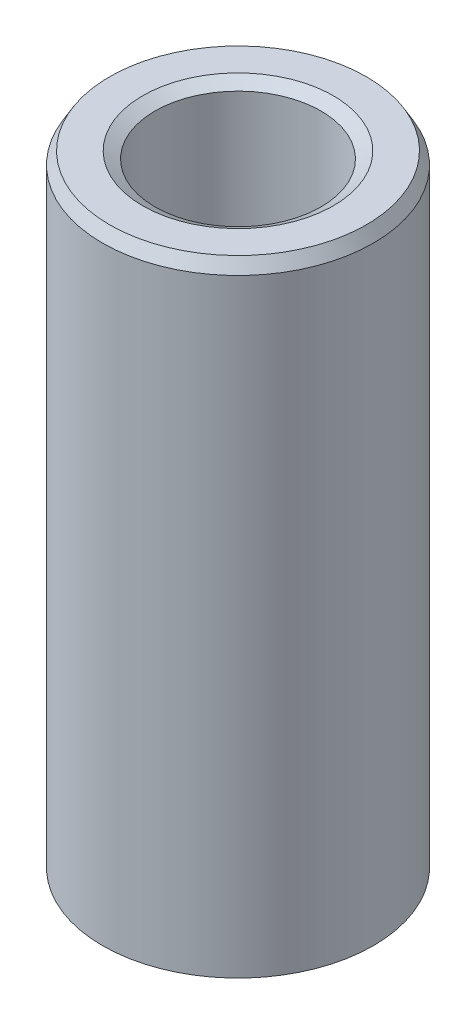
SolidWorks part; units mm, degrees
ref_plane "Front Plane" through (0, 0, 0) normal (0, 0, 1) x (1, 0, 0)
ref_plane "Top Plane" through (0, 0, 0) normal (0, 1, 0) x (1, 0, 0)
ref_plane "Right Plane" through (0, 0, 0) normal (1, 0, 0) x (0, 0, -1)
sketch "Sketch1" plane through (0, 0, 0) normal (0, 1, 0) x (1, 0, 0)
  circle A0 centre (0, 0) radius 42.5
  dimension "SLEEVE_OD" = 85
extrude "Boss-Extrude1" add sketch "Sketch1" along normal blind 197.0313
sketch "Sketch2" plane through (0, 0, 0) normal (0, 1, 0) x (1, 0, 0)
  circle A0 centre (0, 0) radius 26.072
  dimension "BORE_D" = 52.144
extrude "Cut-Extrude1" cut sketch "Sketch2" along normal through all
chamfer "Chamfer1" distance 3.8548 angle 30 4 edges at (0, 197.0313, 26.072) (0, 0, 26.072) (0, 0, 42.5) (0, 197.0313, 42.5) first distance on face at (0, 197.0313, 26.072) first distance on face at (0, 0, 26.072) first distance on face at (0, 197.0313, 42.5)
